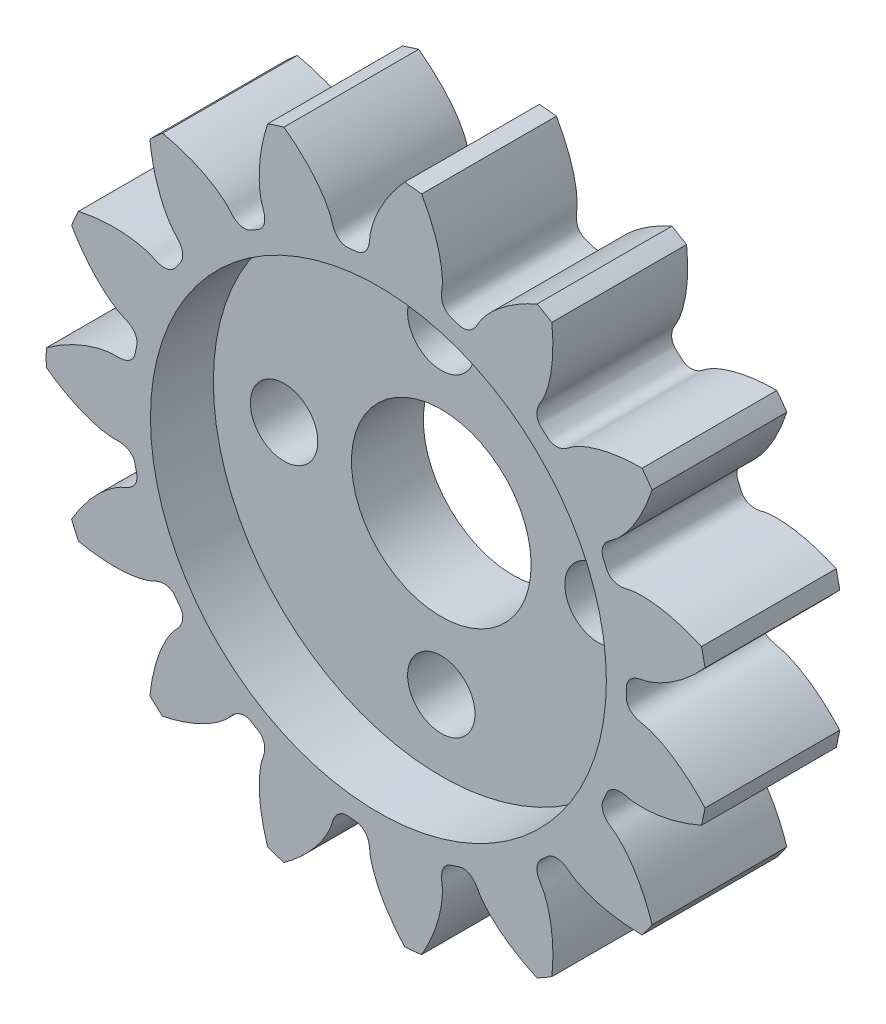
SolidWorks part; units mm, degrees
material "Д16 ГОСТ 4784-97"
ref_plane "FRONT" through (0, 0, 0) normal (0, 0, 1) x (1, 0, 0)
ref_plane "TOP" through (0, 0, 0) normal (0, 1, 0) x (1, 0, 0)
ref_plane "RIGHT" through (0, 0, 0) normal (1, 0, 0) x (0, 0, -1)
ref_axis "Ось1" through (0, 0, 50) along (0, 0, -1)
sketch "SketchRevolveSpurAssembly01Pinion" plane through (0, 0, 0) normal (1, 0, 0) x (0, 0, -1)
  line L0 (0, 0) -> (1, 0) construction
  line L1 (-9.525, 0) -> (-9.525, 14.7917)
  line L2 (-9.525, 14.7917) -> (-3.525, 14.7917)
  line L3 (-3.525, 14.7917) -> (-3.525, 0)
  line L4 (-3.525, 0) -> (-9.525, 0)
  dimension "D1" = 6
revolve "SpurAssembly01Pinion" add sketch "SketchRevolveSpurAssembly01Pinion" angle 360 about L0
sketch "SketchToothSpurAssembly01Pinion" plane through (0, 0, 0) normal (0, 0, 1) x (1, 0, 0)
  arc A0 (14.6389, 2.8106) -> (14.6389, -2.8106) centre (0, 0) cw
  spline S0 degree 3 poles (14.6389, -2.8106) (14.4895, -2.6396) (14.2621, -2.3978) (13.949, -2.1027) (13.726, -1.9083) (13.5095, -1.7341) (13.3007, -1.5791) (13.1009, -1.4425) (12.9111, -1.3233) (12.7324, -1.2205) (12.5656, -1.1331) (12.4118, -1.06) (12.2717, -1) (12.1462, -0.9519) (12.0358, -0.9144) (11.9412, -0.8865) (11.8188, -0.8546) (11.7146, -0.8405) (11.6278, -0.8199) (11.5953, -0.8113) (11.5631, -0.8019) (11.5313, -0.7915) (11.4996, -0.7801) (11.468, -0.7675) (11.4365, -0.7536) (11.4049, -0.7383) (11.3732, -0.7213) (11.3414, -0.7023) (11.3093, -0.6809) (11.2769, -0.6569) (11.2444, -0.6296) (11.2119, -0.5986) (11.1797, -0.5632) (11.1483, -0.5227) (11.1186, -0.4768) (11.0917, -0.4249) (11.0688, -0.3673) (11.0517, -0.3044) (11.0419, -0.2404) (11.0386, -0.1384) (11.0439, 0) (11.0386, 0.1384) (11.0419, 0.2404) (11.0517, 0.3044) (11.0688, 0.3673) (11.0917, 0.4249) (11.1186, 0.4768) (11.1483, 0.5227) (11.1797, 0.5632) (11.2119, 0.5986) (11.2444, 0.6296) (11.2769, 0.6569) (11.3093, 0.6809) (11.3414, 0.7023) (11.3732, 0.7213) (11.4049, 0.7383) (11.4365, 0.7536) (11.468, 0.7675) (11.4996, 0.7801) (11.5313, 0.7915) (11.5631, 0.8019) (11.5953, 0.8113) (11.6278, 0.8199) (11.7146, 0.8405) (11.8188, 0.8546) (11.9412, 0.8865) (12.0358, 0.9144) (12.1462, 0.9519) (12.2717, 1) (12.4118, 1.06) (12.5656, 1.1331) (12.7324, 1.2205) (12.9111, 1.3233) (13.1009, 1.4425) (13.3007, 1.5791) (13.5095, 1.7341) (13.726, 1.9083) (13.949, 2.1027) (14.2621, 2.3978) (14.4895, 2.6396) (14.6389, 2.8106) knots 0 0 0 0 0.071008 0.103709 0.134542 0.163506 0.190601 0.215828 0.239186 0.260675 0.280296 0.298048 0.313931 0.327946 0.340092 0.35037 0.358779 0.37965 0.383168 0.386667 0.390156 0.393647 0.397153 0.400689 0.404271 0.40792 0.411659 0.415515 0.419519 0.423705 0.428112 0.432781 0.437755 0.443073 0.448767 0.454851 0.461317 0.468122 0.475185 0.481526 0.5 0.518474 0.524815 0.531878 0.538683 0.545149 0.551233 0.556927 0.562245 0.567219 0.571888 0.576295 0.580481 0.584485 0.588341 0.59208 0.595729 0.599311 0.602847 0.606353 0.609844 0.613333 0.616832 0.62035 0.641221 0.64963 0.659908 0.672054 0.686069 0.701952 0.719704 0.739325 0.760814 0.784172 0.809399 0.836494 0.865458 0.896291 0.928992 1 1 1 1
extrude "ToothExtrudeCutSpurAssembly01Pinion" cut sketch "SketchToothSpurAssembly01Pinion" against normal blind 9.525 and the other way blind 9.525
pattern_circular "PatternSpurAssembly01Pinion" count 15 every 24 about axis through (0, 0, 50) along (0, 0, -1) of "ToothExtrudeCutSpurAssembly01Pinion"
sketch "Эскиз5" plane through (0, 0, 9.525) normal (0, 0, 1) x (1, 0, 0)
  circle A0 centre (0, 0) radius 10.15
extrude "Вырез-Вытянуть2" cut sketch "Эскиз5" against normal blind 2.8
sketch "Эскиз6" plane through (0, 0, 6.725) normal (0, 0, 1) x (1, 0, 0)
  circle A0 centre (0, 0) radius 7 construction
  circle A1 centre (0, 0) radius 8.5 construction
  circle A2 centre (0, 7) radius 1.5
  circle A3 centre (7, 0) radius 1.5
  circle A4 centre (0, -7) radius 1.5
  circle A5 centre (-7, 0) radius 1.5
  dimension "D1" = 14
  dimension "D2" = 17
extrude "Вырез-Вытянуть3" cut sketch "Эскиз6" against normal blind 5
sketch "Эскиз7" plane through (0, 0, 6.725) normal (0, 0, 1) x (1, 0, 0)
  circle A0 centre (0, 0) radius 4
  dimension "D1" = 8
extrude "Вырез-Вытянуть4" cut sketch "Эскиз7" against normal through all
sketch "AuxiliarySketchSpurAssembly01Pinion" plane through (0, 0, 0) normal (0, 0, 1) x (1, 0, 0)
  circle A0 centre (0, 0) radius 12.5 construction
  circle A1 centre (0, 0) radius 11.7462 construction
  circle A2 centre (0, 0) radius 11.7864 construction
  circle A3 centre (0, 0) radius 14.7917 construction
  circle A4 centre (0, 0) radius 11.0417 construction
  dimension "PitchDiameter" = 25
  dimension "BaseDiameter" = 23.4923
  dimension "FormDiameter" = 23.5728
  dimension "MajorDiameter" = 29.5833
  dimension "MinorDiameter" = 22.0833
